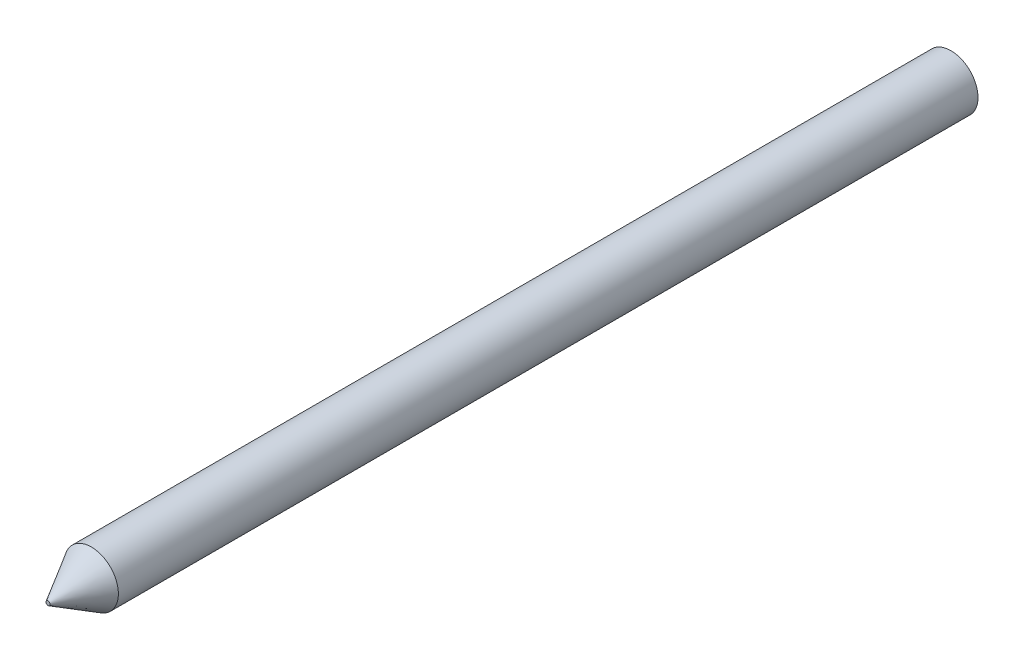
SolidWorks part; units mm, degrees
ref_plane "Front Plane" through (0, 0, 0) normal (0, 0, 1) x (1, 0, 0)
ref_plane "Top Plane" through (0, 0, 0) normal (0, 1, 0) x (1, 0, 0)
ref_plane "Right Plane" through (0, 0, 0) normal (1, 0, 0) x (0, 0, -1)
sketch "Sketch1" plane through (0, 0, 0) normal (0, 0, 1) x (1, 0, 0)
  circle A0 centre (-256.609, 0) radius 7.5
  dimension "D1" = 15
extrude "Boss-Extrude1" add sketch "Sketch1" along normal offset from surface (250.35 mm away) 10
chamfer "Chamfer1" distance 12 angle 30 1 edges at (-249.109, 0, 250.35) first distance on face at (-249.109, 0, 0)
ref_axis "Axis1" through (-256.609, 0, 238.35) along (0, 0, -1)
